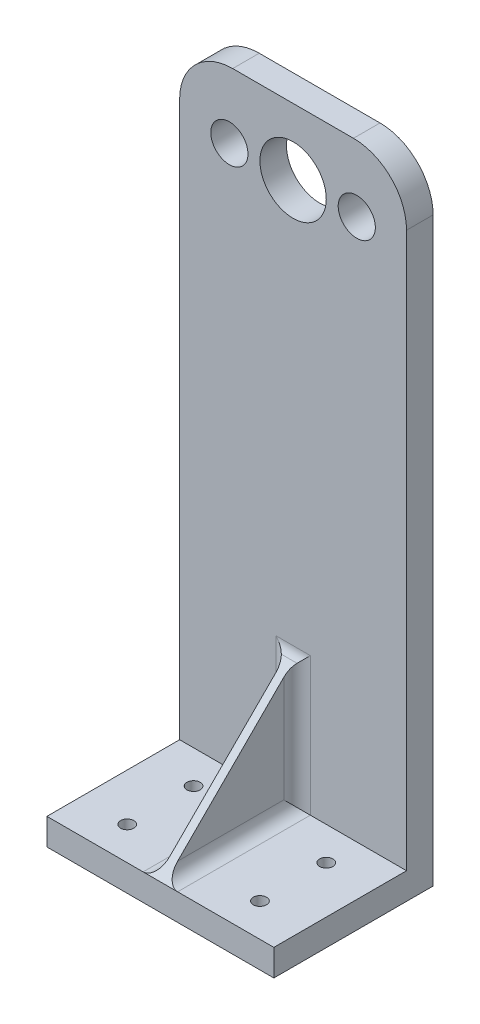
SolidWorks part; units mm, degrees
ref_plane "Front Plane" through (0, 0, 0) normal (0, 0, 1) x (1, 0, 0)
ref_plane "Top Plane" through (0, 0, 0) normal (0, 1, 0) x (1, 0, 0)
ref_plane "Right Plane" through (0, 0, 0) normal (1, 0, 0) x (0, 0, -1)
sketch "Sketch2" plane through (0, 0, 0) normal (0, 0, 1) x (1, 0, 0)
  line L0 (0, 0) -> (0, 38.1) construction
  line L1 (0, 6.35) -> (0, -54.356) construction
  line L2 (0, 0) -> (6.096, 0) construction
  line L3 (0, 0) -> (-6.096, 0) construction
  line L4 (-10.8585, 6.35) -> (10.8585, 6.35)
  line L5 (-10.8585, 6.35) -> (-10.8585, -54.356)
  line L6 (-10.8585, -54.356) -> (10.8585, -54.356)
  line L7 (10.8585, 6.35) -> (10.8585, -54.356)
  circle A0 centre (0, 0) radius 3.175
  circle A1 centre (6.096, 0) radius 1.778
  circle A2 centre (-6.096, 0) radius 1.778
  dimension "D3" = 6.35
  dimension "D5" = 3.556
  dimension "D1" = 38.1
  dimension "D2" = 6.35
  dimension "D4" = 6.096
  dimension "D6" = 4.7625
  dimension "D7" = 60.706
extrude "Boss-Extrude1" add sketch "Sketch2" along normal blind 2.54
sketch "Sketch3" plane through (0, 0, 2.54) normal (0, 0, 1) x (1, 0, 0)
  line L0 (10.8585, -54.356) -> (10.8585, 6.35) construction
  line L1 (-10.8585, -54.356) -> (10.8585, -54.356)
  line L2 (-10.8585, -54.356) -> (-10.8585, -51.816)
  line L3 (-10.8585, -51.816) -> (10.8585, -51.816)
  line L4 (10.8585, -54.356) -> (10.8585, -51.816)
  dimension "D1" = 2.54
extrude "Boss-Extrude2" add sketch "Sketch3" along normal blind 12.7
ref_plane "Plane1" through (0, 0, 0) normal (-1, 0, 0) x (0, 0, 1)
sketch "Sketch5" plane through (0, 0, 0) normal (-1, 0, 0) x (0, 0, 1)
  line L0 (15.24, -51.816) -> (2.54, -51.816)
  line L1 (2.54, -51.816) -> (2.54, -39.116)
  line L2 (2.54, 6.35) -> (2.54, -51.816) construction
  line L3 (2.54, -39.116) -> (15.24, -51.816)
  dimension "D1" = 12.7
  dimension "D2" = 12.7
extrude "Boss-Extrude3" add sketch "Sketch5" along normal blind 0.381 and the other way blind 0.381
sketch "Sketch6" plane through (0, -51.816, 0) normal (0, 1, 0) x (1, 0, 0)
  line L0 (-6.35, -5.715) -> (-10.8585, -5.715) construction
  line L1 (-6.35, -5.715) -> (6.35, -5.715) construction
  line L2 (-6.35, -5.715) -> (-6.35, -12.065) construction
  line L3 (-6.35, -12.065) -> (6.35, -12.065) construction
  line L4 (6.35, -5.715) -> (6.35, -12.065) construction
  line L5 (-10.8585, -15.24) -> (-10.8585, -2.54) construction
  line L6 (6.35, -5.715) -> (10.8585, -5.715) construction
  line L7 (10.8585, -15.24) -> (10.8585, -2.54) construction
  line L8 (-6.35, -5.715) -> (-6.35, -2.54) construction
  line L9 (-0.381, -2.54) -> (-10.8585, -2.54) construction
  line L10 (-6.35, -12.065) -> (-6.35, -15.24) construction
  line L11 (-0.381, -15.24) -> (-10.8585, -15.24) construction
  circle A0 centre (-6.35, -5.715) radius 0.635
  circle A1 centre (6.35, -5.715) radius 0.635
  circle A2 centre (6.35, -12.065) radius 0.635
  circle A3 centre (-6.35, -12.065) radius 0.635
  dimension "D3" = 1.27
  dimension "D1" = 6.35
  dimension "D2" = 12.7
extrude "Cut-Extrude1" cut sketch "Sketch6" against normal through all
fillet "Fillet1" radius 5.08 2 edges at (10.8585, 6.35, 1.27) (-10.8585, 6.35, 1.27)
fillet "Fillet2" radius 1.27 5 edges at (0.381, -45.466, 2.54) (-0.381, -45.466, 2.54) (-0.381, -51.816, 8.89) (0.381, -51.816, 8.89) (0, -39.116, 2.54)
